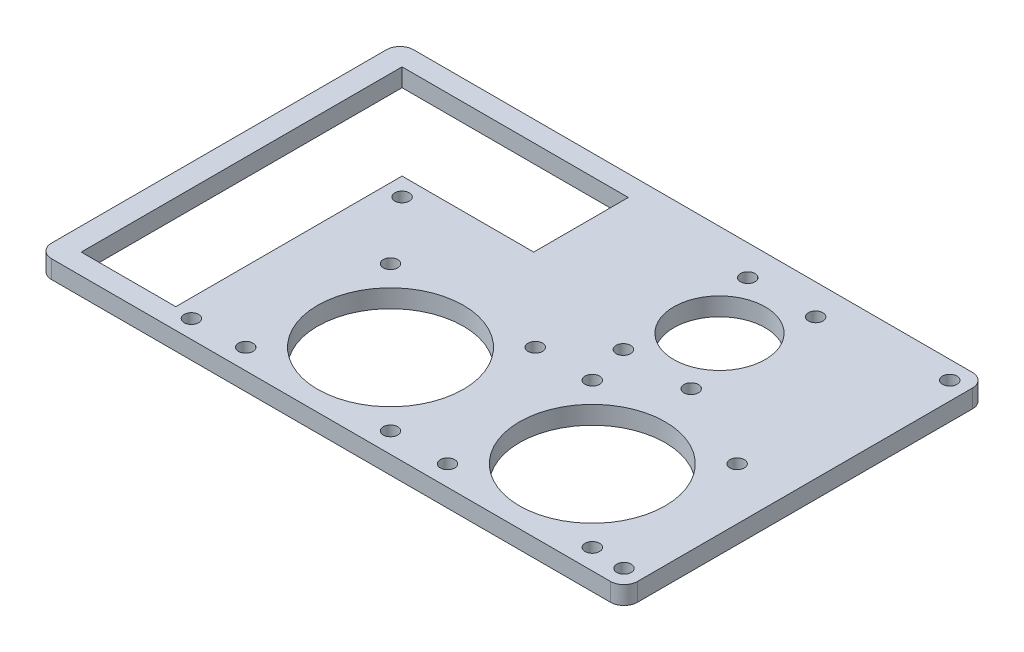
SolidWorks part; units mm, degrees
ref_plane "Front Plane" through (0, 0, 0) normal (0, 0, 1) x (1, 0, 0)
ref_plane "Top Plane" through (0, 0, 0) normal (0, 1, 0) x (1, 0, 0)
ref_plane "Right Plane" through (0, 0, 0) normal (1, 0, 0) x (0, 0, -1)
sketch "Sketch1" plane through (0, 0, 0) normal (0, 1, 0) x (1, 0, 0)
  line L0 (0, 0) -> (129.5, 0)
  line L1 (129.5, 0) -> (129.5, 80)
  line L2 (129.5, 80) -> (0, 80)
  line L3 (0, 80) -> (0, 0)
extrude "Boss-Extrude1" add sketch "Sketch1" along normal blind 4
fillet "Fillet1" radius 3 4 edges at (0, 2, -80) (0, 2, 0) (129.5, 2, -80) (129.5, 2, 0)
sketch "Sketch2" plane through (0, 4, 0) normal (0, 1, 0) x (1, 0, 0)
  line L0 (5, 4.55) -> (25.9, 4.55)
  line L2 (25.9, 4.55) -> (25.9, 54.55)
  line L3 (55, 54.55) -> (25.9, 54.55)
  line L5 (5, 40) -> (5, 4.55)
  line L6 (5, 40) -> (5, 75.45)
  line L7 (5, 75.45) -> (55, 75.45)
  line L9 (55, 75.45) -> (55, 54.55)
  line L10 (0, 77) -> (0, 3) construction
  dimension "D1" = 5
extrude "Cut-Extrude1" cut sketch "Sketch2" against normal blind 10
sketch "Sketch3" plane through (0, 4, 0) normal (0, 1, 0) x (1, 0, 0)
  line L0 (55, 75.45) -> (55, 79.05)
  line L1 (56, 79.05) -> (56, 40.05)
  line L2 (56, 40.05) -> (128, 40.05)
  line L3 (55, 79.05) -> (56, 79.05)
  line L4 (56, 79.05) -> (128, 79.05)
  line L5 (128, 79.05) -> (128, 40.05)
  line L6 (25.9, 4.55) -> (25.9, 0.95)
  line L7 (25.9, 0.95) -> (38.8, 0.95)
  line L8 (38.8, 0.95) -> (38.8, 40.05)
  line L9 (38.8, 40.05) -> (128, 40.05)
  line L10 (128, 40.05) -> (128, 0.95)
  line L11 (128, 0.95) -> (38.8, 0.95)
  circle A0 centre (98.55, 73.3) radius 1.6
  circle A1 centre (83.55, 73.3) radius 1.6
  circle A2 centre (98.55, 45.8) radius 1.6
  circle A3 centre (83.55, 45.8) radius 1.6
  circle A4 centre (91.05, 59.55) radius 10.1
  circle A5 centre (73.4, 36.5) radius 1.6
  circle A6 centre (41.4, 36.5) radius 1.6
  circle A7 centre (73.4, 4.5) radius 1.6
  circle A8 centre (41.4, 4.5) radius 1.6
  circle A9 centre (86, 36.5) radius 1.6
  circle A10 centre (118, 36.5) radius 1.6
  circle A11 centre (118, 4.5) radius 1.6
  circle A12 centre (86, 4.5) radius 1.6
  circle A13 centre (57.4, 20.5) radius 16.1
  circle A14 centre (102, 20.5) radius 16.1
extrude "Cut-Extrude2" cut sketch "Sketch3" against normal blind 10 contours A4 | A1 | A0 | A2 | A3 | A6 | A5 | A9 | A10 | A14 | A13 | A8 | A7 | A12 | A11 region at (98.55, 4, -73.3) region at (83.55, 4, -73.3) region at (98.55, 4, -45.8) region at (83.55, 4, -45.8) region at (91.05, 4, -59.55) region at (73.4, 4, -36.5) region at (41.4, 4, -36.5) region at (73.4, 4, -4.5) region at (41.4, 4, -4.5) region at (86, 4, -36.5) region at (118, 4, -36.5) region at (118, 4, -4.5) region at (86, 4, -4.5) region at (57.4, 4, -20.5) region at (102, 4, -20.5)
sketch "Sketch4" plane through (0, 4, 0) normal (0, 1, 0) x (1, 0, 0)
  circle A0 centre (125.5, 4) radius 1.6
  circle A1 centre (125.5, 76) radius 1.6
  circle A2 centre (29.9, 50.55) radius 1.6
  circle A3 centre (29.9, 4) radius 1.6
extrude "Cut-Extrude3" cut sketch "Sketch4" against normal blind 10
